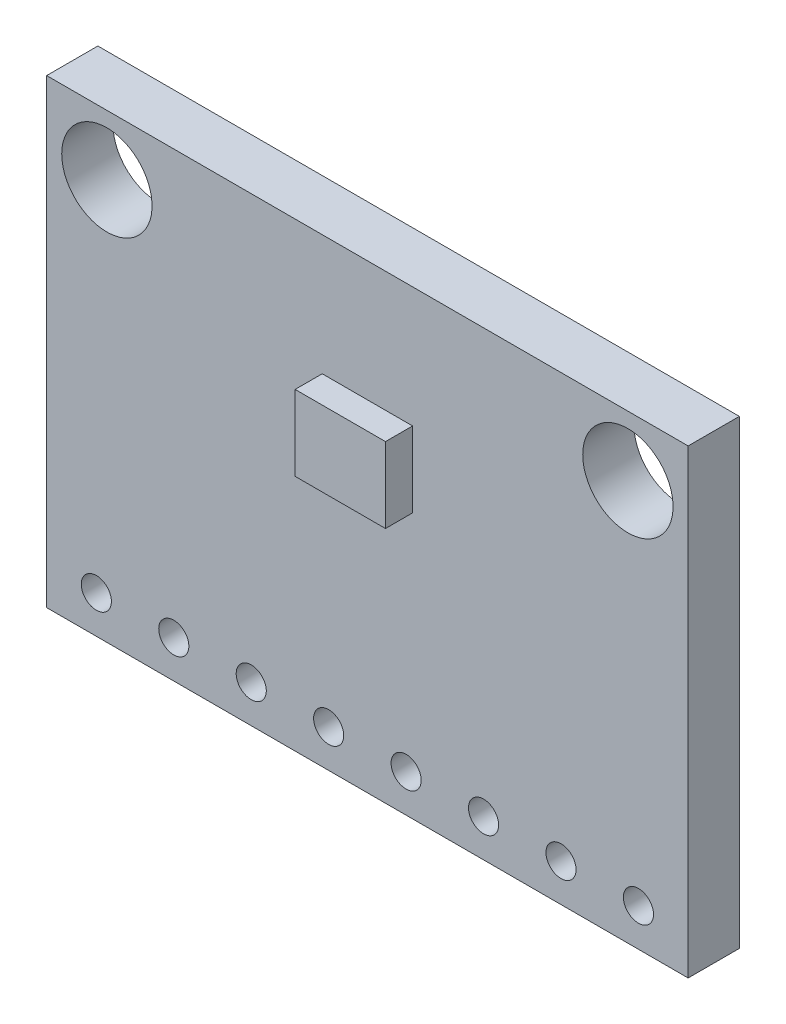
SolidWorks part; units mm, degrees
ref_plane "Front Plane" through (0, 0, 0) normal (0, 0, 1) x (1, 0, 0)
ref_plane "Top Plane" through (0, 0, 0) normal (0, 1, 0) x (1, 0, 0)
ref_plane "Right Plane" through (0, 0, 0) normal (1, 0, 0) x (0, 0, -1)
sketch "Sketch1" plane through (0, 0, 0) normal (0, 0, 1) x (1, 0, 0)
  line L0 (0, 17.7864) -> (0, -14.4965) construction
  line L1 (-26.3198, 0) -> (34.3391, 0) construction
  line L3 (-10.65, 7.65) -> (10.65, 7.65)
  line L4 (-10.65, 7.65) -> (-10.65, -7.65)
  line L5 (-10.65, -7.65) -> (10.65, -7.65)
  line L6 (10.65, 7.65) -> (10.65, -7.65)
  line L7 (-1.5, 3.65) -> (1.5, 3.65)
  line L8 (-1.5, 3.65) -> (-1.5, 1.15)
  line L9 (-1.5, 1.15) -> (1.5, 1.15)
  line L10 (1.5, 3.65) -> (1.5, 1.15)
  circle A0 centre (-8.65, 5.65) radius 1.5
  circle A1 centre (8.65, 5.65) radius 1.5
  circle A2 centre (-9, -6.4) radius 0.5
  circle A3 centre (-6.4286, -6.4) radius 0.5
  circle A4 centre (-3.8571, -6.4) radius 0.5
  circle A5 centre (-1.2857, -6.4) radius 0.5
  circle A6 centre (1.2857, -6.4) radius 0.5
  circle A7 centre (3.8571, -6.4) radius 0.5
  circle A8 centre (6.4286, -6.4) radius 0.5
  circle A9 centre (9, -6.4) radius 0.5
  dimension "D6" = 3
  dimension "D9" = 1
  dimension "D1" = 21.3
  dimension "D2" = 15.3
  dimension "D3" = 3
  dimension "D4" = 2.5
  dimension "D5" = 4
  dimension "D7" = 2
  dimension "D8" = 2
  dimension "D10" = 1.25
  dimension "D12" = 18
  dimension "D11" = 8
extrude "Boss-Extrude1" add sketch "Sketch1" along normal blind 1.7 contours L4 L5 L6 L3
extrude "Boss-Extrude2" add sketch "Sketch1<3>" along normal blind 0.9 from surface contours L10 L9 L8 L7 starting at face at (0, 0, 1.7)
sketch "Sketch1<3>" plane through (0, 0, 0) normal (0, 0, 1) x (1, 0, 0) same geometry as "Sketch1"
extrude "Cut-Extrude1" cut sketch "Sketch1<4>" along normal through all contours A7 | A0 | A1 | A2 | A3 | A4 | A5 | A6 | A8 | A9 region at (3.8571, -6.4, 0)
sketch "Sketch1<4>" plane through (0, 0, 0) normal (0, 0, 1) x (1, 0, 0) same geometry as "Sketch1"
